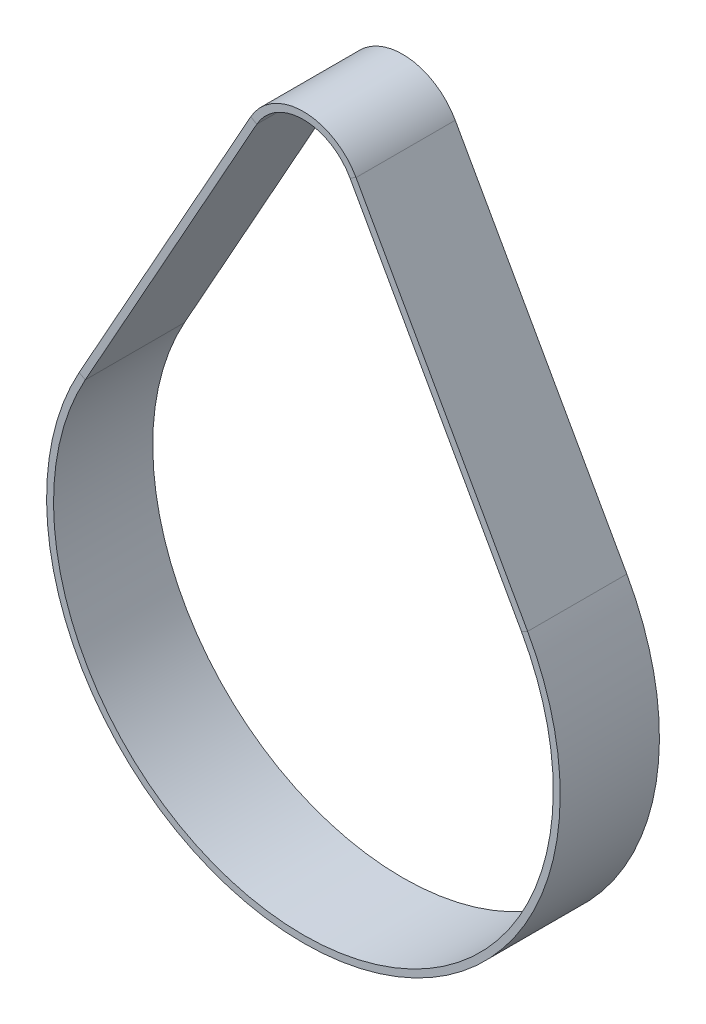
SolidWorks part; units mm, degrees
material "NBR"
ref_plane "Front Plane" through (0, 0, 0) normal (0, 0, 1) x (1, 0, 0)
ref_plane "Top Plane" through (0, 0, 0) normal (0, 1, 0) x (1, 0, 0)
ref_plane "Right Plane" through (0, 0, 0) normal (1, 0, 0) x (0, 0, -1)
sketch "Sketch1" plane through (0, 0, 0) normal (0, 0, 1) x (1, 0, 0)
  line L1 (0, 36.56) -> (0, 0) construction
  line L3 (-4.4466, 39.0431) -> (-20.0097, 11.1742)
  line L4 (20.0097, 11.1742) -> (4.4466, 39.0431)
  arc A0 (-20.0097, 11.1742) -> (20.0097, 11.1742) centre (0, 0) ccw
  arc A1 (4.4466, 39.0431) -> (-4.4466, 39.0431) centre (0, 36.56) ccw
  dimension "D1" = 45.8366
  dimension "D2" = 10.1859
  dimension "D3" = 95.3445
  dimension "D4" = 10.8123
  dimension "D6" = 36.56
ref_axis "Axis1" through (0, 0, -88.99) along (0, 0, 1)
ref_plane "Plane1" through (0, 0, 0) normal (0.4876, -0.8731, 0) x (-0.8731, -0.4876, 0)
sketch "Sketch2" plane through (0, 0, 0) normal (-0.4876, 0.8731, 0) x (0, 0, -1)
  line L0 (4.5, -22.9183) -> (-4.5, -22.9183) construction
  line L1 (4.5, -22.6643) -> (-4.5, -22.6643)
  line L2 (4.5, -22.6643) -> (4.5, -23.2943)
  line L3 (4.5, -23.2943) -> (-4.5, -23.2943)
  line L4 (-4.5, -22.6643) -> (-4.5, -23.2943)
  dimension "D1" = 0.254
  dimension "D2" = 9
  dimension "D3" = 0.63
sweep "Sweep1" add profiles "Sketch2" path "Sketch1"
